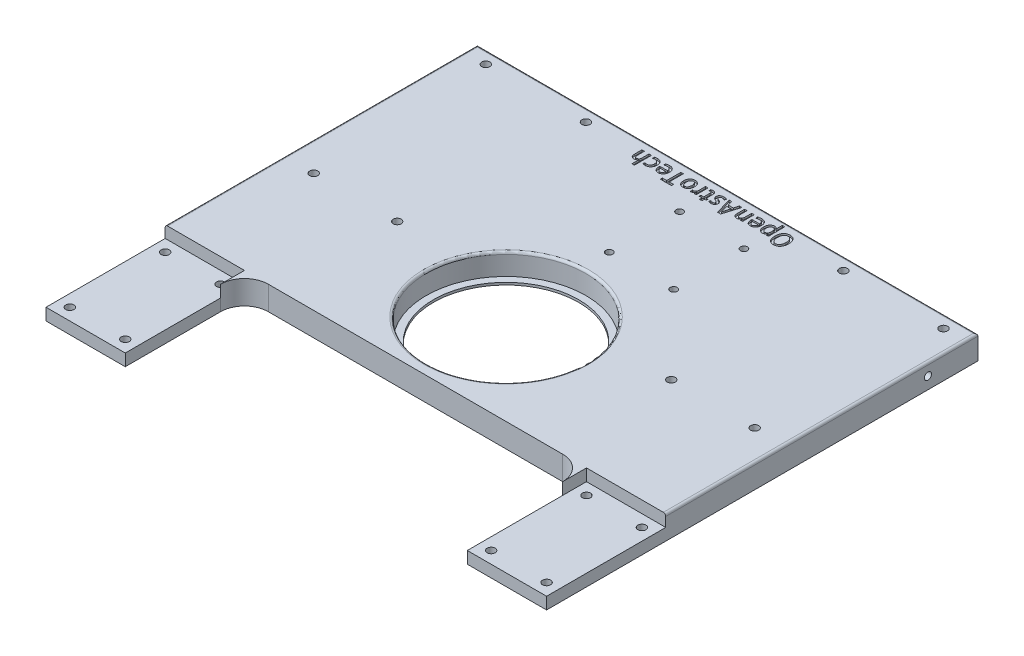
SolidWorks part; units mm, degrees
ref_plane "Ebene vorne" through (0, 0, 0) normal (0, 0, 1) x (1, 0, 0)
ref_plane "Ebene oben" through (0, 0, 0) normal (0, 1, 0) x (1, 0, 0)
ref_plane "Ebene rechts" through (0, 0, 0) normal (1, 0, 0) x (0, 0, -1)
sketch "Skizze1" plane through (0, 0, 0) normal (0, 1, 0) x (1, 0, 0)
  line L1 (-105, -210) -> (105, -210)
  line L2 (-105, -210) -> (-105, 210)
  line L3 (-105, 210) -> (105, 210)
  line L4 (105, -210) -> (105, 210)
  line L5 (-105, -210) -> (105, 210) construction
  line L6 (-105, 210) -> (105, -210) construction
  point P0 (0, 0)
  dimension "D1" = 210
  dimension "D2" = 420
extrude "Aufsatz-Linear austragen1" add sketch "Skizze1" along normal blind 10
ref_plane "Ebene1" through (0, -97.5366, 81.8429) normal (0, -0.766, 0.6428) x (1, 0, 0)
sketch "Skizze2" plane through (0, -97.5366, 81.8429) normal (0, -0.766, 0.6428) x (1, 0, 0)
  line L1 (-105, 167.2972) -> (105, 167.2972) construction
  circle A0 centre (0, 147.2972) radius 5
  dimension "D1" = 10
  dimension "D2" = 20
extrude "Schnitt-Linear austragen1" [suppressed] cut sketch "Skizze2" against normal blind 30 and the other way blind 10
sketch "Skizze3" [suppressed] plane through (0, -67.9923, 57.0523) normal (0, -0.766, 0.6428) x (1, 0, 0)
  circle A0 centre (0, 101.3345) radius 5
  dimension "D1" = 10
extrude "Aufsatz-Linear austragen2" [suppressed] add sketch "Skizze3" along normal blind 0.1
sketch "Skizze4" plane through (0, -97.5366, 81.8429) normal (0, -0.766, 0.6428) x (1, 0, 0)
  line L0 (0, 167.2972) -> (0, 159.9002) construction
  line L1 (-105, 167.2972) -> (105, 167.2972) construction
  line L2 (-25, 167.2972) -> (-25, 202.2972)
  line L3 (-25, 202.2972) -> (25, 202.2972)
  line L4 (-25, 167.2972) -> (25, 167.2972)
  line L5 (25, 167.2972) -> (25, 202.2972)
  point P10 (0, 202.2972)
  dimension "D1" = 50
  dimension "D2" = 35
extrude "Aufsatz-Linear austragen3" [suppressed] add sketch "Skizze4" against normal blind 10 separate body
sketch "Skizze5" plane through (0, 10, 0) normal (0, 1, 0) x (1, 0, 0)
  line L0 (0, 0) -> (0, -210) construction
  line L1 (-105, -210) -> (105, -210) construction
  line L2 (105, -210) -> (18, -210)
  line L3 (-18, -210) -> (-105, -56)
  line L4 (-105, 210) -> (-105, -210) construction
  line L5 (-105, -56) -> (-105, -210)
  line L6 (-105, -210) -> (-18, -210)
  line L7 (105, -56) -> (105, -210)
  line L8 (18, -210) -> (105, -56)
  line L9 (-105, 210) -> (-105, 125)
  line L10 (-105, 125) -> (105, 125)
  line L11 (105, -210) -> (105, 210) construction
  line L12 (105, 125) -> (105, 210)
  line L13 (105, 210) -> (-105, 210)
  line L14 (71.7468, -56) -> (-71.7468, -56)
  line L15 (-71.7468, -56) -> (-2.8247, -178)
  line L16 (71.7468, -56) -> (2.8247, -178)
  line L17 (-2.8247, -178) -> (2.8247, -178)
  line L18 (2.8247, -178) -> (0, -183) construction
  line L19 (-2.8247, -178) -> (0, -183) construction
  point P27 (0, -56)
  dimension "D1" = 36
  dimension "D2" = 154
  dimension "D3" = 85
  dimension "D4" = 32
  dimension "D5" = 27
extrude "Schnitt-Linear austragen2" cut sketch "Skizze5" against normal blind 10
sketch "Skizze6" plane through (0, 10, 0) normal (0, 1, 0) x (1, 0, 0)
  line L0 (0, -210) -> (0, -178) construction
  line L1 (-18, -210) -> (18, -210) construction
  line L2 (-2.8247, -178) -> (2.8247, -178) construction
  line L3 (0, -196.59) -> (-21.075, -196.59) construction
  circle A0 centre (-11, -205) radius 1.7
  circle A1 centre (-11, -188.18) radius 1.7
  circle A2 centre (11, -205) radius 1.7
  circle A3 centre (11, -188.18) radius 1.7
  dimension "D1" = 3.4
  dimension "D2" = 11
  dimension "D3" = 5
  dimension "D4" = 13.41
extrude "Schnitt-Linear austragen3" cut sketch "Skizze6" against normal through all
sketch "Skizze7" plane through (0, 0, 0) normal (0, -1, 0) x (1, 0, 0)
  line L0 (-11, 205) -> (-11, 210) construction
  line L1 (-18, 210) -> (18, 210) construction
  line L2 (-11, 205) -> (-5.1092, 205) construction
  line L3 (-11, 208.4064) -> (-8.05, 206.7032)
  line L4 (-8.05, 206.7032) -> (-8.05, 203.2968)
  line L5 (-11, 201.5936) -> (-8.05, 203.2968)
  line L6 (-11, 201.5936) -> (-13.95, 203.2968)
  line L7 (-13.95, 206.7032) -> (-13.95, 203.2968)
  line L8 (-11, 208.4064) -> (-13.95, 206.7032)
  line L9 (0, 210) -> (0, 121.6034) construction
  line L10 (11, 205) -> (11, 188.18) construction
  line L11 (11, 196.59) -> (0, 196.59) construction
  line L12 (11, 208.4064) -> (8.05, 206.7032)
  line L13 (11, 201.5936) -> (8.05, 203.2968)
  line L14 (8.05, 206.7032) -> (8.05, 203.2968)
  line L15 (11, 201.5936) -> (13.95, 203.2968)
  line L16 (13.95, 206.7032) -> (13.95, 203.2968)
  line L17 (11, 208.4064) -> (13.95, 206.7032)
  line L18 (-8.05, 186.4768) -> (-8.05, 189.8832)
  line L19 (-11, 191.5864) -> (-13.95, 189.8832)
  line L20 (-11, 191.5864) -> (-8.05, 189.8832)
  line L21 (-13.95, 186.4768) -> (-13.95, 189.8832)
  line L22 (-11, 184.7736) -> (-13.95, 186.4768)
  line L23 (-11, 184.7736) -> (-8.05, 186.4768)
  line L24 (8.05, 186.4768) -> (8.05, 189.8832)
  line L25 (11, 191.5864) -> (8.05, 189.8832)
  line L26 (11, 191.5864) -> (13.95, 189.8832)
  line L27 (13.95, 186.4768) -> (13.95, 189.8832)
  line L28 (11, 184.7736) -> (13.95, 186.4768)
  line L29 (11, 184.7736) -> (8.05, 186.4768)
  point P10 (-8.05, 205)
  dimension "D1" = 120
  dimension "D2" = 5.9
extrude "Schnitt-Linear austragen4" cut sketch "Skizze7" against normal blind 4
sketch "Skizze8" plane through (0, 10, 0) normal (0, 1, 0) x (1, 0, 0)
  line L0 (105, 115.41) -> (78.872, 115.41) construction
  line L1 (105, -56) -> (105, 125) construction
  line L2 (-105, 125) -> (105, 125) construction
  dimension "D1" = 9.59
ref_plane "Ebene2" through (0, 62.6966, -52.6087) normal (0, 0.766, -0.6428) x (-1, 0, 0)
sketch "Skizze9" plane through (0, 62.6966, -52.6087) normal (0, 0.766, -0.6428) x (-1, 0, 0)
  line L0 (-105, -81.9813) -> (-78.872, -81.9813) construction
  line L1 (-105, 49.3264) -> (-105, -89.3277) construction
  line L2 (0, -45.2589) -> (0, -16.2619) construction
  circle A0 centre (-100, -81.9813) radius 1.7
  circle A1 centre (100, -81.9813) radius 1.7
  circle A2 centre (-30, -81.9813) radius 1.7
  circle A3 centre (30, -81.9813) radius 1.7
  dimension "D1" = 3.4
  dimension "D2" = 5
  dimension "D3" = 30
extrude "Schnitt-Linear austragen5" [suppressed] cut sketch "Skizze9" against normal through all and the other way through all
ref_plane "Ebene3" through (0, 55.0361, -46.1808) normal (0, 0.766, -0.6428) x (-1, 0, 0)
sketch "Skizze10" [suppressed] plane through (0, 55.0361, -46.1808) normal (0, 0.766, -0.6428) x (-1, 0, 0)
  line L0 (-95, -81.9813) -> (-100, -81.9813) construction
  line L1 (-95, -81.9813) -> (-95, -30.0694) construction
  line L2 (-95, -78.7482) -> (-97.8, -80.3647)
  line L3 (-97.8, -80.3647) -> (-97.8, -83.5979)
  line L4 (-95, -85.2145) -> (-97.8, -83.5979)
  line L5 (-95, -85.2145) -> (-92.2, -83.5979)
  line L6 (-92.2, -80.3647) -> (-92.2, -83.5979)
  line L7 (-95, -78.7482) -> (-92.2, -80.3647)
  line L8 (0, 0) -> (0, -45.6283) construction
  line L9 (-30, -81.9813) -> (-95, -81.9813) construction
  line L10 (-62.5, -81.9813) -> (-62.5, -23.1343) construction
  line L11 (-32.8, -80.3647) -> (-32.8, -83.5979)
  line L12 (-30, -85.2145) -> (-32.8, -83.5979)
  line L13 (-30, -85.2145) -> (-27.2, -83.5979)
  line L14 (-27.2, -80.3647) -> (-27.2, -83.5979)
  line L15 (-30, -78.7482) -> (-27.2, -80.3647)
  line L16 (-30, -78.7482) -> (-32.8, -80.3647)
  line L17 (95, -78.7482) -> (92.2, -80.3647)
  line L18 (92.2, -80.3647) -> (92.2, -83.5979)
  line L19 (95, -85.2145) -> (92.2, -83.5979)
  line L20 (95, -85.2145) -> (97.8, -83.5979)
  line L21 (97.8, -80.3647) -> (97.8, -83.5979)
  line L22 (95, -78.7482) -> (97.8, -80.3647)
  line L23 (30, -78.7482) -> (32.8, -80.3647)
  line L24 (30, -78.7482) -> (27.2, -80.3647)
  line L25 (27.2, -80.3647) -> (27.2, -83.5979)
  line L26 (30, -85.2145) -> (27.2, -83.5979)
  line L27 (30, -85.2145) -> (32.8, -83.5979)
  line L28 (32.8, -80.3647) -> (32.8, -83.5979)
  point P9 (-97.8, -81.9813)
  point P31 (97.8, -81.9813)
  dimension "D1" = 120
  dimension "D2" = 5.6
extrude "Schnitt-Linear austragen6" [suppressed] cut sketch "Skizze10" against normal blind 10 and the other way blind 5
sketch "Skizze13" plane through (0, 10, 0) normal (0, 1, 0) x (1, 0, 0)
  line L0 (71.7468, -56) -> (105, -56) construction
  line L1 (71.7468, -56) -> (96.9548, -70.2409) construction
  line L2 (105, -56) -> (18, -210) construction
  line L3 (0, 0) -> (0, -38.1435) construction
  line L4 (2.8247, -178) -> (71.7468, -56) construction
  line L5 (84.3508, -63.1205) -> (108.762, -19.9098) construction
  line L6 (105, -56) -> (105, 125) construction
  line L7 (88.3734, -56) -> (88.3734, -1) construction
  line L8 (99, -58.9512) -> (105.7595, -46.9862) construction
  line L9 (87.7845, -86.4734) -> (62.5765, -72.2325) construction
  line L10 (77.1638, -80.4734) -> (91.1741, -80.4734) construction
  circle A0 centre (99, -58.9512) radius 1.7
  circle A1 centre (76.9708, -58.9512) radius 1.7
  circle A2 centre (86.8414, -80.4734) radius 1.7
  circle A3 centre (-86.8414, -80.4734) radius 1.7
  circle A4 centre (-99, -58.9512) radius 1.7
  circle A5 centre (-76.9708, -58.9512) radius 1.7
  dimension "D1" = 6
  dimension "D5" = 35
  dimension "D3" = 3.4
  dimension "D6" = 3.4
  dimension "D2" = 6
  dimension "D4" = 6
extrude "Schnitt-Linear austragen7" [suppressed] cut sketch "Skizze13" against normal through all
sketch "Skizze14" plane through (103.579, 0, 58.5154) normal (0.8707, 0, 0.4919) x (0.4919, 0, -0.8707)
  line L0 (-32.111, 5) -> (-32.111, 10)
  line L5 (2.889, 0) -> (2.889, 10) construction
  line L6 (-32.111, 5) -> (2.889, 5)
  line L7 (2.889, 10) -> (-173.9866, 10) construction
  line L8 (-32.111, 10) -> (2.889, 10)
  line L9 (2.889, 10) -> (2.889, 5)
  dimension "D1" = 35
extrude "Schnitt-Linear austragen8" [suppressed] cut sketch "Skizze14" against normal up to surface (28.9525 mm away)
mirror "Spiegeln1" [suppressed] about plane through (0, 0, 0) normal (1, 0, 0)
sketch "Skizze15" [suppressed] plane through (95, 0, 0) normal (1, 0, 0) x (0, 0, -1)
  line L0 (4, 10) -> (4, 0)
  line L1 (4, 0) -> (65, 0)
  line L2 (65, 0) -> (65, 10)
  line L3 (65, 10) -> (4, 10)
extrude "Schnitt-Linear austragen9" [suppressed] cut sketch "Skizze15" against normal through all
sketch "Skizze16" plane through (0, 0, 0) normal (0, -1, 0) x (1, 0, 0)
  line L0 (0, 210) -> (0, 178) construction
  line L1 (-18, 210) -> (18, 210) construction
  line L2 (-2.8247, 178) -> (2.8247, 178) construction
  line L3 (11, 196.59) -> (0, 196.59) construction
  line L4 (11, 205) -> (11, 188.18) construction
  line L6 (-17.5, 193.09) -> (17.5, 193.09)
  line L7 (-17.5, 193.09) -> (-17.5, 200.09)
  line L8 (-17.5, 200.09) -> (17.5, 200.09)
  line L9 (17.5, 193.09) -> (17.5, 200.09)
  line L10 (-17.5, 193.09) -> (17.5, 200.09) construction
  line L11 (-17.5, 200.09) -> (17.5, 193.09) construction
  dimension "D1" = 7
  dimension "D2" = 35
extrude "Schnitt-Linear austragen10" cut sketch "Skizze16" against normal blind 5
sketch "Skizze17" plane through (17.5, 0, 0) normal (-1, 0, 0) x (0, 0, 1)
  line L0 (196.59, 0) -> (196.59, 11.1261) construction
  line L1 (193.09, 0) -> (200.09, 0) construction
  line L2 (193.09, 5) -> (196.59, 8.5)
  line L3 (196.59, 8.5) -> (200.09, 5)
  line L4 (200.09, 5) -> (193.09, 5)
  dimension "D1" = 90
extrude "Schnitt-Linear austragen11" cut sketch "Skizze17" along normal up to surface (35 mm away) up to face at (-17.5, 2.5, 196.59)
sketch "Skizze18" [suppressed] plane through (0, 10, 0) normal (0, 1, 0) x (1, 0, 0)
  line L0 (0, -210) -> (0, 0) construction
  line L1 (-18, -210) -> (18, -210) construction
  line L2 (62.5765, -72.2325) -> (35.4483, -67.5372)
  line L3 (15.3378, -155.8503) -> (-22.1774, -134.6566)
  line L4 (2.8247, -178) -> (62.5765, -72.2325) construction
  line L5 (-15.3378, -155.8503) -> (22.1774, -134.6566)
  line L6 (58.6594, -79.166) -> (40.7308, -76.063)
  line L7 (0, -147.1854) -> (19.5429, -147.1854) construction
  line L8 (0, -95.4) -> (31.4297, -95.4) construction
  line L9 (11.6488, -162.3803) -> (0, -155.7995)
  line L10 (-71.7468, -56) -> (-2.8247, -178) construction
  line L11 (0, -95.4) -> (-37.5153, -116.5937) construction
  line L12 (-37.5153, -116.5937) -> (-39.2566, -117.5774) construction
  line L13 (-11.6488, -162.3803) -> (0, -155.7995)
  line L14 (-58.6594, -79.166) -> (-40.7308, -76.063)
  line L15 (-62.5765, -72.2325) -> (-35.4483, -67.5372)
  circle A0 centre (0, -95.4) radius 33.5
  arc A1 (7.4594, -151.3994) -> (7.4594, -142.9713) centre (9.84, -147.1854) cw
  arc A2 (-7.4594, -151.3994) -> (-7.4594, -142.9713) centre (-9.84, -147.1854) ccw
  circle A3 centre (0, -95.4) radius 45.0879
  point P17 (0, -147.1854)
  point P36 (5, -147.1854)
  point P40 (-5, -147.1854)
  line M16 (62.5765, -72.2325) -> (2.8247, -178)
  line M18 (-2.8247, -178) -> (-71.7468, -56)
  dimension "D2" = 67
  dimension "D5" = 2
  dimension "D4" = 10
  dimension "D1" = 114.6
  dimension "D3" = 7.5
  dimension "D6" = 7.5
extrude "Aufsatz-Linear austragen4" [suppressed] add sketch "Skizze18" against normal blind 10 contours A3 L15 L14 M18 | A3 A0 M16 M18 | A3 L6 L2 M16 | A2 L5 L3 | A3 L3 L5 | L3 A1 L5 | L13 L9 L3 L5 M18 M16
sketch "Skizze19" [suppressed] plane through (0, 0, 0) normal (0, -1, 0) x (1, 0, 0)
  circle A0 centre (0, 35.4) radius 31.5
  circle A1 centre (0, 35.4) radius 33.5
  circle A2 centre (0, 35.4) radius 33.5 construction
  dimension "D1" = 63
extrude "Aufsatz-Linear austragen5" [suppressed] add sketch "Skizze19" against normal blind 1
sketch "Skizze20" plane through (0, 10, 0) normal (0, 1, 0) x (1, 0, 0)
  line L0 (105, 119.52) -> (55.4083, 119.52) construction
  line L1 (105, -56) -> (105, 125) construction
  line L2 (-105, 125) -> (105, 125) construction
  line L3 (0, 125) -> (0, 96.9732) construction
  line L4 (105, 43.82) -> (35.5869, 43.82) construction
  circle A0 centre (96, 119.52) radius 1.7
  circle A1 centre (54, 119.52) radius 1.7
  circle A2 centre (-54, 119.52) radius 1.7
  circle A3 centre (-96, 119.52) radius 1.7
  circle A4 centre (92.5, 43.82) radius 1.7
  circle A5 centre (57.5, 43.82) radius 1.7
  circle A6 centre (-92.5, 43.82) radius 1.7
  circle A7 centre (-57.5, 43.82) radius 1.7
  dimension "D1" = 3.4
  dimension "D2" = 5.48
  dimension "D3" = 9
  dimension "D4" = 42
  dimension "D5" = 75.7
  dimension "D6" = 12.5
  dimension "D7" = 35
extrude "Schnitt-Linear austragen12" cut sketch "Skizze20" against normal through all
sketch "Skizze21" plane through (0, 10, 0) normal (0, 1, 0) x (1, 0, 0)
  line L0 (-71.7468, -56) -> (-71.7468, -6)
  line L1 (-71.7468, -6) -> (71.7468, -6)
  line L2 (71.7468, -6) -> (71.7468, -56)
  line L3 (71.7468, -56) -> (-71.7468, -56) construction
  line L4 (-71.7468, -56) -> (71.7468, -56)
  dimension "D1" = 50
extrude "Schnitt-Linear austragen13" cut sketch "Skizze21" against normal through all
sketch "Skizze22" plane through (0, 10, 0) normal (0, 1, 0) x (1, 0, 0)
  line L0 (-71.7468, -56) -> (-2.8247, -178)
  arc A0 (-71.7468, -56) -> (-2.8247, -178) centre (55.7113, -64.4627) ccw
  line M19 (-2.8247, -178) -> (-71.7468, -56)
extrude "Schnitt-Linear austragen14" cut sketch "Skizze22" against normal through all contours M19 region at (-44.6278, 10, 121.1478)
sketch "Skizze23" plane through (0, 10, 0) normal (0, 1, 0) x (1, 0, 0)
  line L0 (-18, -210) -> (-105, -56) construction
  line L1 (-105, -56) -> (-18, -210)
  arc A0 (-18, -210) -> (-105, -56) centre (108.9155, -36.7263) cw
  arc A2 (-71.7468, -56) -> (-2.8247, -178) centre (55.7113, -64.4627) ccw construction
  dimension "D1" = 60
extrude "Aufsatz-Linear austragen6" add sketch "Skizze23" against normal blind 10
mirror "Spiegeln2" about plane through (0, 0, 0) normal (1, 0, 0) of "Aufsatz-Linear austragen6", "Schnitt-Linear austragen14"
sketch "Skizze25" plane through (0, 10, 0) normal (0, 1, 0) x (1, 0, 0)
  line L0 (-105, -56) -> (-71.7468, -56) construction
  line L1 (-105, -6) -> (-105, -56) construction
  line L2 (-105, -6) -> (-71.7468, -6) construction
  line L3 (-71.7468, -6) -> (-71.7468, -56) construction
  line L4 (-88.3734, -6) -> (-88.3734, -56) construction
  line L5 (-105, -31) -> (-71.7468, -31) construction
  line L6 (-105, 125) -> (-105, -56) construction
  circle A0 centre (-100, -11) radius 1.7
  circle A1 centre (-76.7468, -11) radius 1.7
  circle A2 centre (-76.7468, -51) radius 1.7
  circle A3 centre (-100, -51) radius 1.7
  dimension "D2" = 3.4
  dimension "D1" = 50
  dimension "D3" = 5
  dimension "D4" = 5
extrude "Schnitt-Linear austragen15" cut sketch "Skizze25" against normal through all
sketch "Skizze26" plane through (-105, 0, 0) normal (-1, 0, 0) x (0, 0, 1)
  line L0 (6, 5) -> (6, 13.1015)
  line L1 (56, 0) -> (56, 10) construction
  line L2 (56, 5) -> (6, 5)
  line L4 (-125, 0) -> (56, 0) construction
  line L5 (56, 5) -> (56, 0)
  line L6 (6, 13.1015) -> (200.6846, 82.5463)
  line L7 (200.6846, 82.5463) -> (242.9972, -41.0376)
  line L8 (242.9972, -41.0376) -> (91.2415, -60.2848)
  line L9 (91.2415, -60.2848) -> (56, 0)
  dimension "D1" = 50
mirror "Spiegeln3" about plane through (0, 0, 0) normal (1, 0, 0) of "Schnitt-Linear austragen15"
extrude "Schnitt-Linear austragen16" cut sketch "Skizze26" against normal through all
sketch "Skizze27" plane through (0, 10, 0) normal (0, 1, 0) x (1, 0, 0)
  line L0 (0, -6) -> (0, 125) construction
  line L1 (105, -6) -> (-105, -6) construction
  line L2 (-105, 125) -> (105, 125) construction
  line L3 (105, -6) -> (-105, -6) construction
  circle A0 centre (0, 32) radius 33.5
  dimension "D1" = 67
  dimension "D2" = 38
extrude "Schnitt-Linear austragen17" cut sketch "Skizze27" against normal through all
sketch "Skizze28" plane through (0, 0, 0) normal (0, -1, 0) x (1, 0, 0)
  circle A0 centre (0, -32) radius 30.5
  circle A1 centre (0, -32) radius 33.5 construction
  circle A2 centre (0, -32) radius 36.0063
  dimension "D1" = 3
extrude "Aufsatz-Linear austragen7" add sketch "Skizze28" against normal blind 1
sketch "Skizze29" plane through (-105, 0, 0) normal (-1, 0, 0) x (0, 0, 1)
  line L0 (-125, 5) -> (-93.4233, 5) construction
  line L1 (-125, 0) -> (-125, 10) construction
  circle A0 centre (-104, 5) radius 1.5
  dimension "D1" = 3
  dimension "D2" = 21
extrude "Schnitt-Linear austragen18" cut sketch "Skizze29" against normal blind 10
sketch "Skizze30" plane through (0, 0, -125) normal (0, 0, -1) x (-1, 0, 0)
  line L0 (105, 5) -> (60.2539, 5) construction
  line L1 (105, 0) -> (105, 10) construction
  circle A0 centre (100, 5) radius 1.5
  circle A1 centre (84, 5) radius 1.5
  dimension "D1" = 3
  dimension "D2" = 5
  dimension "D3" = 21
extrude "Schnitt-Linear austragen19" cut sketch "Skizze30" against normal blind 10
mirror "Spiegeln4" about plane through (0, 0, 0) normal (1, 0, 0) of "Schnitt-Linear austragen18", "Schnitt-Linear austragen19"
sketch "Skizze31" plane through (0, 0, 0) normal (0, -1, 0) x (1, 0, 0)
  line L0 (0, -125) -> (0, -73.0202) construction
  line L1 (-105, -125) -> (105, -125) construction
  circle A0 centre (-96, -119.52) radius 2.95
  circle A1 centre (-54, -119.52) radius 2.95
  circle A2 centre (-92.5, -43.82) radius 2.95
  circle A3 centre (-57.5, -43.82) radius 2.95
  circle A4 centre (57.5, -43.82) radius 2.95
  circle A5 centre (92.5, -43.82) radius 2.95
  circle A6 centre (54, -119.52) radius 2.95
  circle A7 centre (96, -119.52) radius 2.95
  dimension "D1" = 5.9
extrude "Schnitt-Linear austragen20" cut sketch "Skizze31" against normal blind 3.5
move or copy body "Körper-Verschieben/Kopieren1" [suppressed] bodies to move or copy 132 copy no rotation origin (0, 5, -34.5) rotation axis (1, 0, 0) rotation angle 90
sketch "Skizze32" plane through (0, 10, 0) normal (0, 1, 0) x (1, 0, 0)
  line L1 (25.1613, 106.641) -> (-1.8387, 106.641)
  line L2 (25.1613, 106.641) -> (25.1613, 77.141)
  line L3 (25.1613, 77.141) -> (-1.8387, 77.141)
  line L4 (-1.8387, 106.641) -> (-1.8387, 77.141)
  line L5 (25.1613, 106.641) -> (-1.8387, 77.141) construction
  line L6 (25.1613, 77.141) -> (-1.8387, 106.641) construction
  circle A0 centre (25.1613, 77.141) radius 1.45
  circle A1 centre (-1.8387, 77.141) radius 1.45
  circle A2 centre (-1.8387, 106.641) radius 1.45
  circle A3 centre (25.1613, 106.641) radius 1.45
  point P0 (11.6613, 91.891)
  dimension "D3" = 2.9
  dimension "D1" = 29.5
  dimension "D2" = 27
extrude "Schnitt-Linear austragen21" cut sketch "Skizze32" against normal through all contours L3 A0 L2 | L2 A0 L3 | L4 A1 L3 | L3 A1 L4 | L1 A2 L4 | L4 A2 L1 | L2 A3 L1 | L1 A3 L2 region at (-1.2233, 10, -106.0256) region at (-2.0439, 10, -106.8462) region at (25.3664, 10, -106.8462) region at (24.5459, 10, -106.0256) region at (-1.2233, 10, -77.7564) region at (-2.0439, 10, -76.9359) region at (25.3664, 10, -76.9359) region at (24.5459, 10, -77.7564)
fillet "Verrundung1" radius 10 2 edges at (-71.7468, 2.5, 6) (71.7468, 2.5, 6)
sketch "Skizze33" plane through (0, 5, 0) normal (0, 1, 0) x (1, 0, 0)
  line L0 (-71.7468, -16) -> (-71.7468, -6)
  line L1 (-61.7468, -6) -> (-105, -6) construction
  line L2 (-71.7468, -6) -> (-61.7468, -6)
  line L3 (105, -6) -> (-105, -6) construction
  line L4 (0, -6) -> (0, -39.688) construction
  line L5 (71.7468, -6) -> (61.7468, -6)
  line L6 (71.7468, -16) -> (71.7468, -6)
  arc A0 (-61.7468, -6) -> (-71.7468, -16) centre (-61.7468, -16) ccw construction
  arc A1 (-71.7468, -16) -> (-61.7468, -6) centre (-61.7468, -16) cw
  arc A2 (71.7468, -16) -> (61.7468, -6) centre (61.7468, -16) ccw
extrude "Aufsatz-Linear austragen8" add sketch "Skizze33" along normal up to surface (5 mm away) up to face at (-1.8387, 10, -75.691)
fillet "Verrundung2" radius 1 4 edges at (0, 10, 1.5) (105, 10, -59.5) (0, 10, -125) (-105, 10, -59.5)
sketch "Skizze34" plane through (0, 10, 0) normal (0, 1, 0) x (1, 0, 0)
  line L0 (54, 121.22) -> (-54, 121.22) construction
  circle A0 centre (-54, 119.52) radius 1.7 construction
  circle A1 centre (54, 119.52) radius 1.7 construction
  text T0 "OpenAstroTech" font "@Adobe Heiti Std R" height in points 22
extrude "Schnitt-Linear austragen22" cut sketch "Skizze34" against normal blind 0.8
